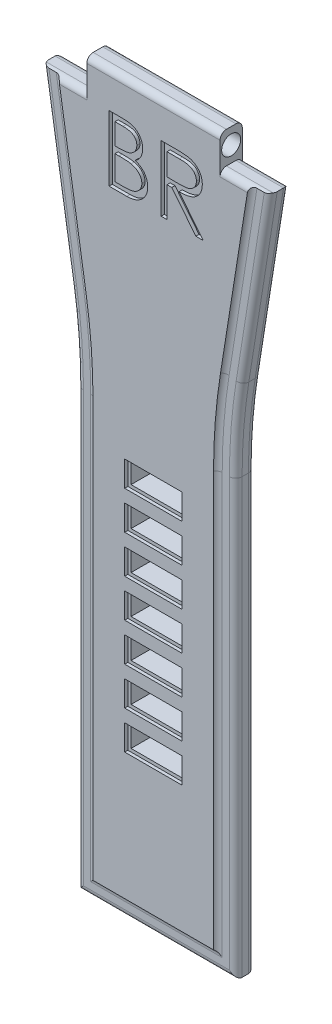
SolidWorks part; units mm, degrees
ref_plane "Alzado" through (0, 0, 0) normal (0, 0, 1) x (1, 0, 0)
ref_plane "Planta" through (0, 0, 0) normal (0, 1, 0) x (1, 0, 0)
ref_plane "Vista lateral" through (0, 0, 0) normal (1, 0, 0) x (0, 0, -1)
sketch "Croquis1" plane through (0, 0, 0) normal (0, 0, 1) x (1, 0, 0)
  line L0 (0, 0) -> (21, 0)
  line L1 (21, 0) -> (21, -5)
  line L2 (21, -5) -> (28.5, -5)
  line L3 (28.5, -5) -> (22.9718, -39.9037)
  line L4 (-7.5, -5) -> (-2.0259, -39.5623)
  line L5 (-2.0259, -39.5623) -> (-2.0259, -115.0023)
  line L6 (-7.5, -5) -> (0, -5)
  line L7 (0, -5) -> (0, 0)
  line L9 (-2.0259, -115.0023) -> (22.9718, -115.0023)
  line L10 (22.9718, -39.9037) -> (22.9718, -115.0023)
  dimension "D1" = 21
  dimension "D2" = 5
  dimension "D3" = 5
  dimension "D4" = 7.5
  dimension "D5" = 7.5
  dimension "D6" = 25
  dimension "D7" = 81
  dimension "D8" = 81
  dimension "D9" = 34.5623
  dimension "D10" = 75.44
extrude "Saliente-Extruir1" add sketch "Croquis1" along normal blind 3.5
fillet "Redondeo1" radius 86 2 edges at (-2.0259, -39.5623, 1.75) (22.9718, -39.9037, 1.75)
sketch "Croquis2" plane through (0, 0, 3.5) normal (0, 0, 1) x (1, 0, 0)
  line L5 (24.0306, -33.2187) -> (28.5, -5) construction
  line L6 (-7.5, -5) -> (-3.0847, -32.8773) construction
  line L7 (-2.0259, -46.3306) -> (-2.0259, -115.0023) construction
  line L8 (22.9718, -115.0023) -> (22.9718, -46.672) construction
  line L9 (-2.0259, -115.0023) -> (22.9718, -115.0023) construction
  line L10 (-4.4626, -5) -> (-0.1216, -32.408)
  line L11 (0.9741, -46.3306) -> (0.9741, -112.0023)
  line L12 (0.9741, -112.0023) -> (19.9718, -112.0023)
  line L13 (19.9718, -112.0023) -> (19.9718, -46.672)
  line L14 (21.0675, -32.7494) -> (25.4626, -5)
  line L15 (24.0306, -33.2187) -> (28.5, -5)
  line L16 (-7.5, -5) -> (-3.0847, -32.8773)
  line L17 (-2.0259, -46.3306) -> (-2.0259, -115.0023)
  line L18 (22.9718, -115.0023) -> (22.9718, -46.672)
  line L19 (-2.0259, -115.0023) -> (22.9718, -115.0023)
  line L20 (-7.5, -5) -> (-4.4626, -5)
  line L21 (0, -5) -> (-7.5, -5) construction
  line L22 (25.4626, -5) -> (28.5, -5)
  line L23 (-4.5369, -4.5307) -> (-0.1216, -32.408) construction
  line L25 (21.0675, -32.7494) -> (25.5369, -4.5307) construction
  arc A0 (-2.0259, -46.3306) -> (-3.0847, -32.8773) centre (-88.0259, -46.3306) ccw construction
  arc A1 (24.0306, -33.2187) -> (22.9718, -46.672) centre (108.9718, -46.672) ccw construction
  arc A2 (-2.0259, -46.3306) -> (-3.0847, -32.8773) centre (-88.0259, -46.3306) ccw
  arc A3 (24.0306, -33.2187) -> (22.9718, -46.672) centre (108.9718, -46.672) ccw
  arc A4 (0.9741, -46.3306) -> (-0.1216, -32.408) centre (-88.0259, -46.3306) ccw
  arc A5 (21.0675, -32.7494) -> (19.9718, -46.672) centre (108.9718, -46.672) ccw
  dimension "D1" = 3
extrude "Cortar-Extruir1" cut sketch "Croquis2" against normal blind 0.5
fillet "Redondeo2" radius 1 7 edges at (23.2651, -18.8747, 3) (20.2462, -39.6892, 3) (0.9741, -79.1665, 3) (0.6998, -39.3478, 3) (19.9718, -79.3372, 3) (10.473, -112.0023, 3) (-2.2921, -18.704, 3)
fillet "Redondeo3" radius 1 20 edges at (26.2653, -19.1093, 0) (23.2369, -39.9246, 0) (26.2653, -19.1093, 3) (23.2369, -39.9246, 3) (-5.2923, -18.9386, 0) (-2.291, -39.5832, 0) (-5.2923, -18.9386, 3) (-2.291, -39.5832, 3) (24.75, -5, 0) (23.2313, -5, 3.5) (10.5, 0, 0) (10.5, 0, 3.5) (-3.75, -5, 0) (-2.2313, -5, 3.5) (10.473, -115.0023, 0) (10.473, -115.0023, 3) (22.9718, -80.8372, 0) (22.9718, -80.8372, 3) (-2.0259, -80.6665, 0) (-2.0259, -80.6665, 3)
ref_plane "Plano1" through (21, 0, 0) normal (1, 0, 0) x (0, 0, -1)
sketch "Croquis3" plane through (21, 0, 0) normal (1, 0, 0) x (0, 0, -1)
  line L0 (-1.75, -5) -> (-1.75, 0) construction
  line L1 (-2.5, -5) -> (-1, -5) construction
  line L2 (-2.5, 0) -> (-1, 0) construction
  circle A0 centre (-1.75, -2.5) radius 1.5
  dimension "D1" = 3
extrude "Cortar-Extruir3" cut sketch "Croquis3" against normal through all
ref_plane "Plano2" through (0, 0, 3.5) normal (0, 0, 1) x (1, 0, 0)
sketch "Croquis4" plane through (0, 0, 3.5) normal (0, 0, 1) x (1, 0, 0)
  line L0 (10.473, -115.0023) -> (10.473, -90.0023) construction
  line L1 (22.9718, -115.0023) -> (-2.0259, -115.0023) construction
  line L3 (6.473, -88.5023) -> (14.473, -88.5023)
  line L4 (6.473, -88.5023) -> (6.473, -91.5023)
  line L5 (6.473, -91.5023) -> (14.473, -91.5023)
  line L6 (14.473, -88.5023) -> (14.473, -91.5023)
  line L7 (6.473, -88.5023) -> (14.473, -91.5023) construction
  line L8 (6.473, -91.5023) -> (14.473, -88.5023) construction
  dimension "D1" = 25
  dimension "D2" = 8
  dimension "D3" = 3
extrude "Cortar-Extruir4" cut sketch "Croquis4" against normal through all
pattern_linear "MatrizL1" count 7 spacing 6 along (0, 1, 0) of "Cortar-Extruir4"
ref_plane "Plano3" through (0, 0, 3.5) normal (0, 0, 1) x (1, 0, 0)
sketch "Croquis5" plane through (0, 0, 3.5) normal (0, 0, 1) x (1, 0, 0)
  line L0 (6.473, -91.5023) -> (14.473, -91.5023) construction
  line L1 (14.473, -91.5023) -> (14.473, -88.5023) construction
  line L2 (14.473, -88.5023) -> (6.473, -88.5023) construction
  line L3 (6.473, -88.5023) -> (6.473, -91.5023) construction
  line L4 (6.473, -85.5023) -> (14.473, -85.5023) construction
  line L5 (6.473, -82.5023) -> (6.473, -85.5023) construction
  line L6 (14.473, -82.5023) -> (6.473, -82.5023) construction
  line L7 (14.473, -85.5023) -> (14.473, -82.5023) construction
  line L8 (14.473, -79.5023) -> (14.473, -76.5023) construction
  line L9 (6.473, -79.5023) -> (14.473, -79.5023) construction
  line L10 (6.473, -76.5023) -> (6.473, -79.5023) construction
  line L11 (14.473, -76.5023) -> (6.473, -76.5023) construction
  line L12 (14.473, -70.5023) -> (6.473, -70.5023) construction
  line L13 (6.473, -70.5023) -> (6.473, -73.5023) construction
  line L14 (6.473, -73.5023) -> (14.473, -73.5023) construction
  line L15 (14.473, -73.5023) -> (14.473, -70.5023) construction
  line L16 (14.473, -67.5023) -> (14.473, -64.5023) construction
  line L17 (14.473, -64.5023) -> (6.473, -64.5023) construction
  line L18 (6.473, -64.5023) -> (6.473, -67.5023) construction
  line L19 (6.473, -67.5023) -> (14.473, -67.5023) construction
  line L20 (6.473, -61.5023) -> (14.473, -61.5023) construction
  line L21 (14.473, -58.5023) -> (6.473, -58.5023) construction
  line L22 (14.473, -61.5023) -> (14.473, -58.5023) construction
  line L23 (6.473, -58.5023) -> (6.473, -61.5023) construction
  line L24 (6.473, -52.5023) -> (6.473, -55.5023) construction
  line L25 (14.473, -52.5023) -> (6.473, -52.5023) construction
  line L26 (14.473, -55.5023) -> (14.473, -52.5023) construction
  line L27 (6.473, -55.5023) -> (14.473, -55.5023) construction
  line L28 (6.473, -91.5023) -> (14.473, -91.5023)
  line L29 (14.473, -91.5023) -> (14.473, -88.5023)
  line L30 (14.473, -88.5023) -> (6.473, -88.5023)
  line L31 (6.473, -88.5023) -> (6.473, -91.5023)
  line L32 (6.473, -85.5023) -> (14.473, -85.5023)
  line L33 (6.473, -82.5023) -> (6.473, -85.5023)
  line L34 (14.473, -82.5023) -> (6.473, -82.5023)
  line L35 (14.473, -85.5023) -> (14.473, -82.5023)
  line L36 (14.473, -79.5023) -> (14.473, -76.5023)
  line L37 (6.473, -79.5023) -> (14.473, -79.5023)
  line L38 (6.473, -76.5023) -> (6.473, -79.5023)
  line L39 (14.473, -76.5023) -> (6.473, -76.5023)
  line L40 (14.473, -70.5023) -> (6.473, -70.5023)
  line L41 (6.473, -70.5023) -> (6.473, -73.5023)
  line L42 (6.473, -73.5023) -> (14.473, -73.5023)
  line L43 (14.473, -73.5023) -> (14.473, -70.5023)
  line L44 (14.473, -67.5023) -> (14.473, -64.5023)
  line L45 (14.473, -64.5023) -> (6.473, -64.5023)
  line L46 (6.473, -64.5023) -> (6.473, -67.5023)
  line L47 (6.473, -67.5023) -> (14.473, -67.5023)
  line L48 (6.473, -61.5023) -> (14.473, -61.5023)
  line L49 (14.473, -58.5023) -> (6.473, -58.5023)
  line L50 (14.473, -61.5023) -> (14.473, -58.5023)
  line L51 (6.473, -58.5023) -> (6.473, -61.5023)
  line L52 (6.473, -52.5023) -> (6.473, -55.5023)
  line L53 (14.473, -52.5023) -> (6.473, -52.5023)
  line L54 (14.473, -55.5023) -> (14.473, -52.5023)
  line L55 (6.473, -55.5023) -> (14.473, -55.5023)
  line L56 (14.973, -52.0023) -> (5.973, -52.0023)
  line L57 (5.973, -52.0023) -> (5.973, -56.0023)
  line L58 (5.973, -56.0023) -> (14.973, -56.0023)
  line L59 (14.973, -56.0023) -> (14.973, -52.0023)
  line L60 (14.973, -58.0023) -> (5.973, -58.0023)
  line L61 (5.973, -58.0023) -> (5.973, -62.0023)
  line L62 (5.973, -62.0023) -> (14.973, -62.0023)
  line L63 (14.973, -62.0023) -> (14.973, -58.0023)
  line L64 (14.973, -64.0023) -> (5.973, -64.0023)
  line L65 (5.973, -64.0023) -> (5.973, -68.0023)
  line L66 (5.973, -68.0023) -> (14.973, -68.0023)
  line L67 (14.973, -68.0023) -> (14.973, -64.0023)
  line L68 (14.973, -70.0023) -> (5.973, -70.0023)
  line L69 (5.973, -70.0023) -> (5.973, -74.0023)
  line L70 (5.973, -74.0023) -> (14.973, -74.0023)
  line L71 (14.973, -74.0023) -> (14.973, -70.0023)
  line L72 (14.973, -76.0023) -> (5.973, -76.0023)
  line L73 (5.973, -76.0023) -> (5.973, -80.0023)
  line L74 (5.973, -80.0023) -> (14.973, -80.0023)
  line L75 (14.973, -80.0023) -> (14.973, -76.0023)
  line L76 (14.973, -82.0023) -> (5.973, -82.0023)
  line L77 (5.973, -82.0023) -> (5.973, -86.0023)
  line L78 (5.973, -86.0023) -> (14.973, -86.0023)
  line L79 (14.973, -86.0023) -> (14.973, -82.0023)
  line L80 (14.973, -88.0023) -> (5.973, -88.0023)
  line L81 (5.973, -88.0023) -> (5.973, -92.0023)
  line L82 (5.973, -92.0023) -> (14.973, -92.0023)
  line L83 (14.973, -92.0023) -> (14.973, -88.0023)
  dimension "D1" = 0.5
extrude "Cortar-Extruir5" cut sketch "Croquis5" against normal blind 0.5
ref_plane "Plano4" through (0, 0, 3.5) normal (0, 0, 1) x (1, 0, 0)
sketch "Croquis6" plane through (0, 0, 3.5) normal (0, 0, 1) x (1, 0, 0)
  line L0 (10.5, -1) -> (10.5, -16) construction
  line L1 (21, -1) -> (0, -1) construction
  line L2 (2.193, -16) -> (19.5325, -16) construction
  text T0 "BR" font "Century Gothic" height in points 39
  dimension "D1" = 15
extrude "Cortar-Extruir6" cut sketch "Croquis6" against normal blind 0.5
